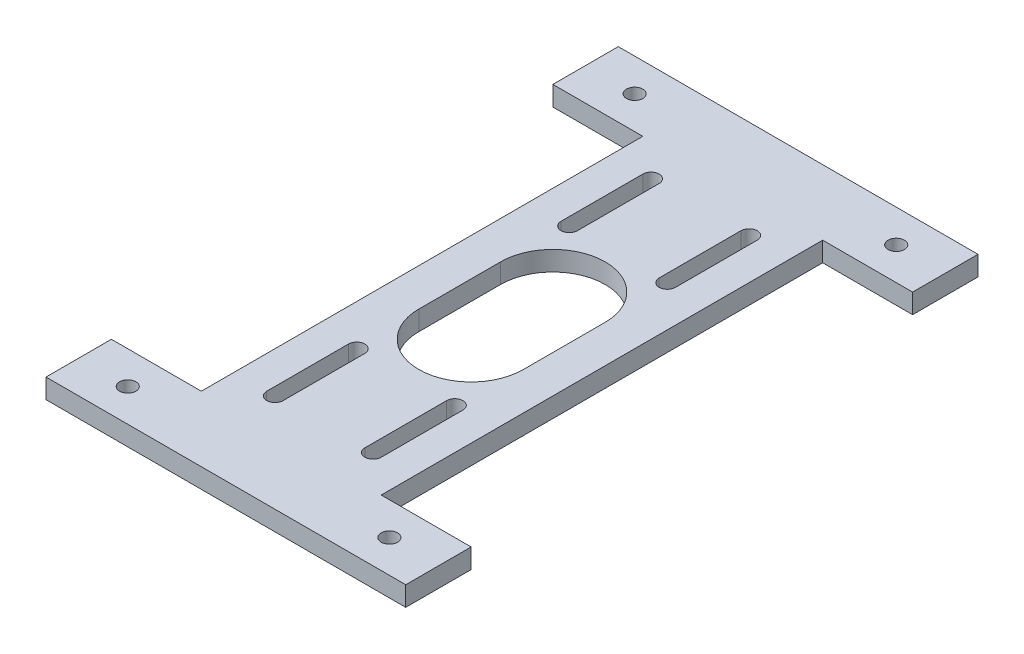
SolidWorks part; units mm, degrees
ref_plane "Front Plane" through (0, 0, 0) normal (0, 0, 1) x (1, 0, 0)
ref_plane "Top Plane" through (0, 0, 0) normal (0, 1, 0) x (1, 0, 0)
ref_plane "Right Plane" through (0, 0, 0) normal (1, 0, 0) x (0, 0, -1)
sketch "Sketch1" plane through (0, 0, 0) normal (0, 1, 0) x (1, 0, 0)
  line L0 (0, -12.5) -> (0, 12.5) construction
  line L1 (-27.5, 67.5) -> (27.5, 67.5)
  line L2 (-27.5, 67.5) -> (-27.5, -67.5)
  line L3 (-27.5, -67.5) -> (27.5, -67.5)
  line L4 (27.5, 67.5) -> (27.5, -67.5)
  line L5 (-27.5, 67.5) -> (27.5, -67.5) construction
  line L6 (-27.5, -67.5) -> (27.5, 67.5) construction
  line L7 (-16, -12.5) -> (-16, 12.5)
  line L8 (16, -12.5) -> (16, 12.5)
  line L9 (-15, -32.5) -> (-15, -57.5) construction
  line L10 (-12.5, -32.5) -> (-12.5, -57.5)
  line L11 (-17.5, -32.5) -> (-17.5, -57.5)
  line L12 (-55, 0) -> (55, 0) construction
  line L13 (-55, -87.5) -> (55, -87.5)
  line L14 (-55, -87.5) -> (-55, -67.5)
  line L15 (-55, -67.5) -> (55, -67.5)
  line L16 (55, -87.5) -> (55, -67.5)
  line L17 (-55, -87.5) -> (55, -67.5) construction
  line L18 (-55, -67.5) -> (55, -87.5) construction
  line L19 (-15, 32.5) -> (-15, 57.5) construction
  line L20 (-12.5, 32.5) -> (-12.5, 57.5)
  line L21 (-17.5, 32.5) -> (-17.5, 57.5)
  line L22 (0, -55) -> (0, 55) construction
  line L23 (15, -32.5) -> (15, -57.5) construction
  line L24 (12.5, -32.5) -> (12.5, -57.5)
  line L25 (17.5, -32.5) -> (17.5, -57.5)
  line L26 (15, 32.5) -> (15, 57.5) construction
  line L27 (12.5, 32.5) -> (12.5, 57.5)
  line L28 (17.5, 32.5) -> (17.5, 57.5)
  line L29 (-55, 67.5) -> (55, 67.5)
  line L30 (55, 87.5) -> (55, 67.5)
  line L31 (-55, 87.5) -> (55, 87.5)
  line L32 (-55, 87.5) -> (-55, 67.5)
  arc A1 (-16, -12.5) -> (16, -12.5) centre (0, -12.5) ccw
  arc A2 (16, 12.5) -> (-16, 12.5) centre (0, 12.5) ccw
  arc A3 (-12.5, -32.5) -> (-17.5, -32.5) centre (-15, -32.5) ccw
  arc A4 (-17.5, -57.5) -> (-12.5, -57.5) centre (-15, -57.5) ccw
  arc A6 (-12.5, 32.5) -> (-17.5, 32.5) centre (-15, 32.5) cw
  arc A7 (-17.5, 57.5) -> (-12.5, 57.5) centre (-15, 57.5) cw
  arc A8 (12.5, -32.5) -> (17.5, -32.5) centre (15, -32.5) cw
  arc A9 (17.5, -57.5) -> (12.5, -57.5) centre (15, -57.5) cw
  arc A10 (12.5, 32.5) -> (17.5, 32.5) centre (15, 32.5) ccw
  arc A11 (17.5, 57.5) -> (12.5, 57.5) centre (15, 57.5) ccw
  circle A12 centre (-40, -77.5) radius 2.5
  circle A13 centre (40, -77.5) radius 2.5
  circle A14 centre (40, 77.5) radius 2.5
  circle A15 centre (-40, 77.5) radius 2.5
  point P0 (0, 0)
  point P2 (0, 87.5)
  point P9 (0, 0)
  point P16 (-15, -45)
  point P21 (0, -77.5)
  point P30 (-15, 45)
  point P39 (15, -45)
  point P46 (15, 45)
  point P57 (-55, -77.5)
  dimension "D1" = 55
  dimension "D3" = 16
  dimension "D5" = 2.5
  dimension "D9" = 5
  dimension "D2" = 135
  dimension "D4" = 25
  dimension "D6" = 20
  dimension "D7" = 45
  dimension "D8" = 15
  dimension "D10" = 40
  dimension "D11" = 110
extrude "Boss-Extrude1" add sketch "Sketch1" along normal blind 6 contours L13 L16 L15 L3 L14 | L4 L1 L2 L3 A4 L11 A3 L10 A2 L8 A1 L7 | L31 L32 L29 L1 L30 A14 A15 region at (0, 0, -77.5) region at (0, 0, -66.0423) region at (0, 0, 77.5)
sketch "Sketch2" plane through (0, 0, 0) normal (0, 1, 0) x (1, 0, 0)
  line L0 (0, -55) -> (0, 55) construction
  line L1 (-55, 0) -> (55, 0) construction
  circle A0 centre (-40, 77.5) radius 6
  circle A1 centre (40, 77.5) radius 6
  circle A2 centre (40, -77.5) radius 6
  circle A3 centre (-40, -77.5) radius 6
  dimension "D1" = 12
